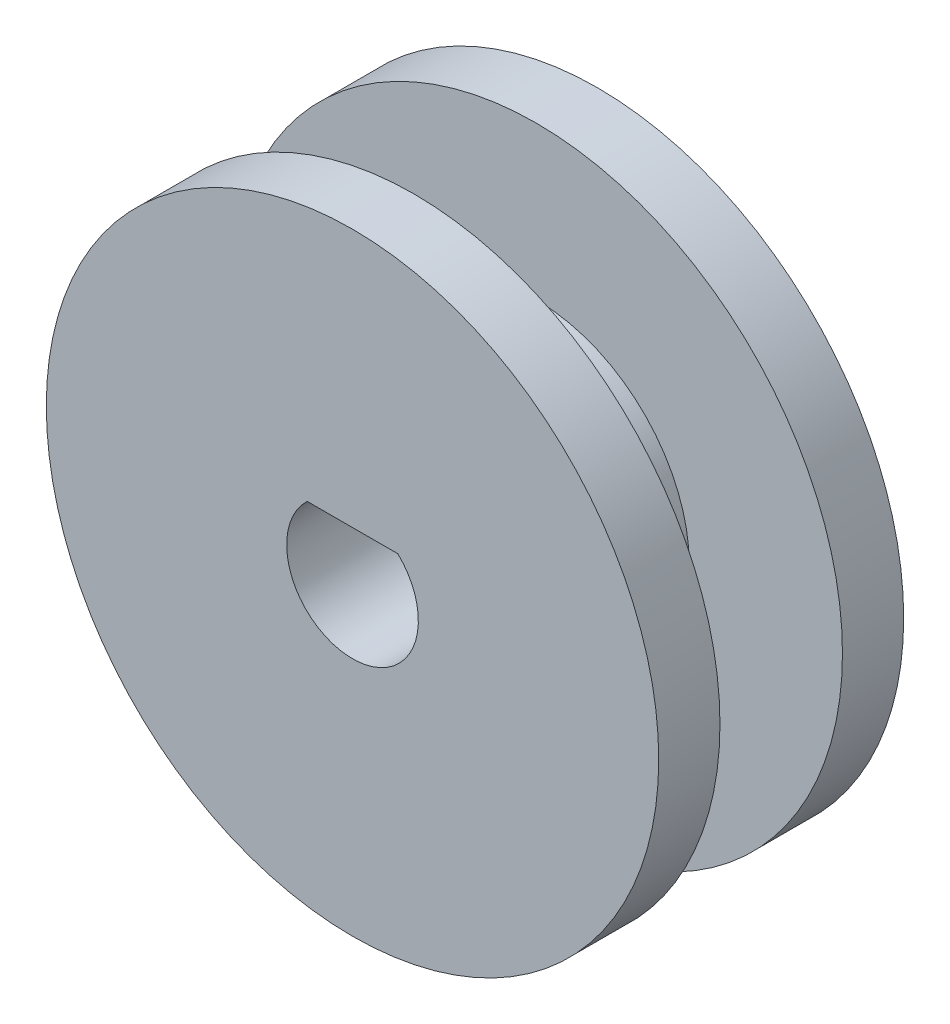
SolidWorks part; units mm, degrees
ref_plane "Front Plane" through (0, 0, 0) normal (0, 0, 1) x (1, 0, 0)
ref_plane "Top Plane" through (0, 0, 0) normal (0, 1, 0) x (1, 0, 0)
ref_plane "Right Plane" through (0, 0, 0) normal (1, 0, 0) x (0, 0, -1)
sketch "Sketch1" plane through (0, 0, 0) normal (0, 0, 1) x (1, 0, 0)
  circle A0 centre (0, 0) radius 10
  dimension "D1" = 20
extrude "Boss-Extrude1" add sketch "Sketch1" along normal blind 2
sketch "Sketch2" plane through (0, 0, 2) normal (0, 0, 1) x (1, 0, 0)
  circle A0 centre (0, 0) radius 5
  dimension "D1" = 10
extrude "Boss-Extrude2" add sketch "Sketch2" along normal blind 4
sketch "Sketch3" plane through (0, 0, 6) normal (0, 0, 1) x (1, 0, 0)
  circle A0 centre (0, 0) radius 10
  dimension "D1" = 20
extrude "Boss-Extrude3" add sketch "Sketch3" along normal blind 2
sketch "Sketch6" plane through (0, 0, 8) normal (0, 0, 1) x (1, 0, 0)
  line L1 (-2.8577, 3.5542) -> (3.2144, 3.5542)
  line L2 (-2.8577, 3.5542) -> (-2.8577, 1.56)
  line L3 (-2.8577, 1.56) -> (3.2144, 1.56)
  line L4 (3.2144, 3.5542) -> (3.2144, 1.56)
  circle A0 centre (0, 0) radius 2.15
  dimension "D1" = 4.3
  dimension "D2" = 1.56
extrude "Cut-Extrude1" cut sketch "Sketch6" against normal through all contours L3 A0 region at (0, -0.1621, 8)
